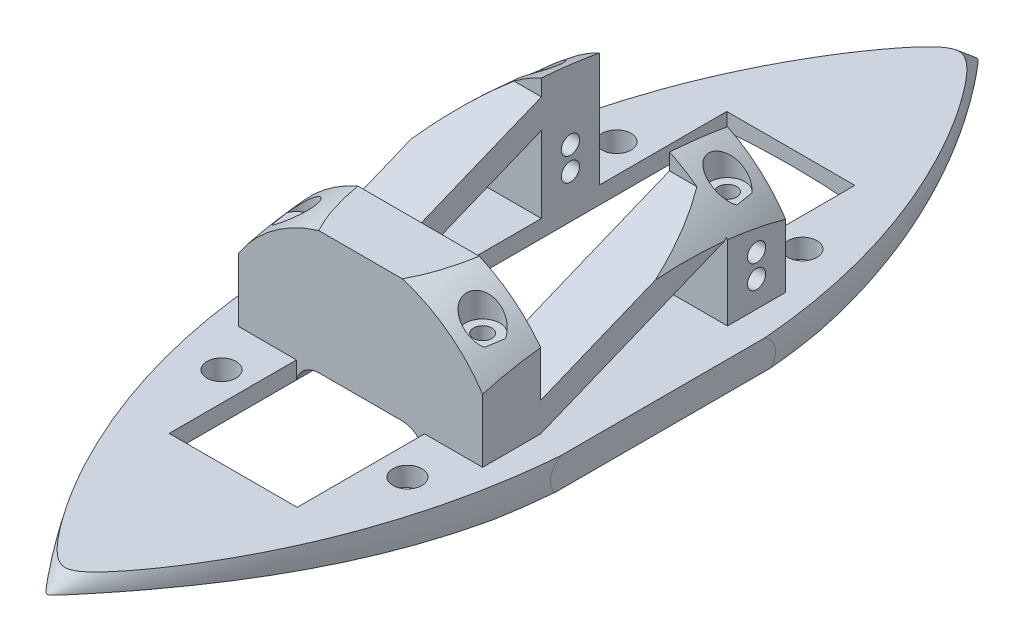
SolidWorks part; units mm, degrees
material "Custom Plastic"
ref_plane "Front Plane" through (0, 0, 0) normal (0, 0, 1) x (1, 0, 0)
ref_plane "Top Plane" through (0, 0, 0) normal (0, 1, 0) x (1, 0, 0)
ref_plane "Right Plane" through (0, 0, 0) normal (1, 0, 0) x (0, 0, -1)
sketch "Sketch2" plane through (0, 0, 0) normal (0, 0, 1) x (1, 0, 0)
  line L1 (-16.51, 1.5875) -> (16.51, 1.5875)
  line L2 (-16.51, 1.5875) -> (-16.51, -1.5875)
  line L3 (-16.51, -1.5875) -> (16.51, -1.5875)
  line L4 (16.51, 1.5875) -> (16.51, -1.5875)
  line L5 (-16.51, 1.5875) -> (16.51, -1.5875) construction
  line L6 (-16.51, -1.5875) -> (16.51, 1.5875) construction
  point P0 (0, 0)
  dimension "D1" = 3.175
  dimension "D2" = 33.02
extrude "Boss-Extrude1" add sketch "Sketch2" along normal blind 101.6
sketch "Sketch3" plane through (0, 0, 101.6) normal (0, 0, 1) x (1, 0, 0)
  line L0 (0, 0) -> (0, -78.359) construction
  circle A0 centre (0, -78.359) radius 78.359
  dimension "D1" = 78.359
extrude "Cut-Extrude1" cut sketch "Sketch3" against normal through all
sketch "Sketch5" plane through (0, 1.5875, 0) normal (0, 1, 0) x (1, 0, 0)
  line L0 (0, 0) -> (0, -34.925) construction
  line L1 (6.9977, -44.4246) -> (10.1727, -44.4246) construction
  line L2 (-6.9977, -25.4254) -> (6.9977, -25.4254) construction
  line L3 (-6.9977, -25.4254) -> (-6.9977, -44.4246) construction
  line L4 (-6.9977, -44.4246) -> (6.9977, -44.4246) construction
  line L5 (6.9977, -25.4254) -> (6.9977, -44.4246) construction
  line L6 (-6.9977, -25.4254) -> (6.9977, -44.4246) construction
  line L7 (-6.9977, -44.4246) -> (6.9977, -25.4254) construction
  line L8 (10.1727, -44.4246) -> (10.1727, -37.4142) construction
  line L9 (-13.3477, -40.5892) -> (-6.9977, -40.5892)
  line L10 (13.3477, -40.5892) -> (6.9977, -40.5892)
  line L11 (13.3477, -40.5892) -> (13.3477, -34.2392)
  line L12 (13.3477, -34.2392) -> (6.9977, -34.2392)
  line L13 (6.9977, -40.5892) -> (6.9977, -34.2392)
  line L14 (13.3477, -40.5892) -> (6.9977, -34.2392) construction
  line L15 (13.3477, -34.2392) -> (6.9977, -40.5892) construction
  line L16 (-6.9977, -40.5892) -> (-6.9977, -34.2392)
  line L17 (-13.3477, -40.5892) -> (-6.9977, -34.2392) construction
  line L18 (-13.3477, -34.2392) -> (-6.9977, -40.5892) construction
  line L19 (-13.3477, -34.2392) -> (-6.9977, -34.2392)
  line L20 (-13.3477, -40.5892) -> (-13.3477, -34.2392)
  line L21 (-10.1727, -44.4246) -> (-10.1727, -37.4142) construction
  line L22 (-6.9977, -44.4246) -> (-10.1727, -44.4246) construction
  line L23 (-16.51, -50.8) -> (16.51, -50.8) construction
  line L24 (-16.51, -101.6) -> (-16.51, 0) construction
  line L25 (16.51, -101.6) -> (16.51, 0) construction
  line L26 (-13.3477, -61.0108) -> (-6.9977, -61.0108)
  line L27 (-13.3477, -67.3608) -> (-6.9977, -61.0108) construction
  line L28 (-13.3477, -61.0108) -> (-6.9977, -67.3608) construction
  line L29 (-6.9977, -61.0108) -> (-6.9977, -67.3608)
  line L30 (-13.3477, -67.3608) -> (-6.9977, -67.3608)
  line L31 (-13.3477, -61.0108) -> (-13.3477, -67.3608)
  line L32 (13.3477, -67.3608) -> (6.9977, -61.0108) construction
  line L33 (13.3477, -61.0108) -> (6.9977, -67.3608) construction
  line L34 (6.9977, -61.0108) -> (6.9977, -67.3608)
  line L35 (13.3477, -67.3608) -> (6.9977, -67.3608)
  line L36 (13.3477, -61.0108) -> (13.3477, -67.3608)
  line L37 (13.3477, -61.0108) -> (6.9977, -61.0108)
  dimension "D1" = 13.9954
  dimension "D2" = 18.9992
  dimension "D3" = 34.925
  dimension "D4" = 3.175
  dimension "D5" = 7.0104
  dimension "D6" = 6.35
extrude "Boss-Extrude2" add sketch "Sketch5" along normal blind 15.24
sketch "Sketch6" plane through (13.3477, 0, 0) normal (1, 0, 0) x (0, 0, -1)
  line L0 (-61.0108, 1.5875) -> (-40.5892, 1.5875) construction
  line L1 (-40.5892, 1.5875) -> (-40.5892, 9.923) construction
  line L2 (-40.5892, 16.8275) -> (-40.5892, 1.5875) construction
  line L3 (-40.5892, 9.923) -> (-40.5892, 13.098) construction
  line L4 (-61.0108, 1.5875) -> (-61.0108, 4.7625) construction
  line L5 (-61.0108, 16.8275) -> (-61.0108, 1.5875) construction
  line L10 (-61.0108, 1.5875) -> (-61.0108, 4.7625)
  line L11 (-61.0108, 1.5875) -> (-40.5892, 9.923)
  line L12 (-61.0108, 4.7625) -> (-40.5892, 13.098)
  line L13 (-40.5892, 9.923) -> (-40.5892, 13.098)
  dimension "D1" = 8.3355
  dimension "D2" = 3.175
sketch "Sketch13" plane through (6.9977, 0, 0) normal (-1, 0, 0) x (0, 0, 1)
  line L0 (67.3608, 16.8275) -> (67.3608, 1.5875) construction
  line L9 (61.0108, 1.5875) -> (67.3608, 1.5875)
  line L10 (61.0108, 1.5875) -> (61.0108, 15.0495)
  line L11 (61.0108, 15.0495) -> (67.3608, 15.0495)
  line L12 (67.3608, 1.5875) -> (67.3608, 15.0495)
  dimension "D1" = 13.462
extrude "Boss-Extrude5" add sketch "Sketch13" along normal up to surface (13.9954 mm away) up to face at (-6.9977, 9.2075, 37.4142)
extrude "Boss-Extrude3" add sketch "Sketch6" against normal blind 6.35
sketch "Sketch4" plane through (0, 0, 0) normal (1, 0, 0) x (0, 0, -1)
  line L0 (0, 0) -> (-48.26, 0) construction
  line L1 (-48.26, 0) -> (-48.26, 16.51) construction
  line L2 (-48.26, 16.51) -> (-53.34, 16.51)
  line L3 (-50.8, 16.51) -> (-50.8, 0) construction
  line L4 (-48.26, 0) -> (-53.34, 0) construction
  line L5 (-101.6, 0) -> (-53.34, 0) construction
  line L6 (0, 0) -> (-101.6, 0) construction
  line L7 (0, 0) -> (0, -0.254) construction
  line L8 (0, -1.5875) -> (0, 1.5875) construction
  line L9 (0, -0.254) -> (-101.6, -0.254) construction
  line L10 (0, 0) -> (0, 25.4)
  line L11 (0, 25.4) -> (-101.6, 25.4)
  line L12 (-101.6, 25.4) -> (-101.6, 0)
  arc A0 (-48.26, 16.51) -> (0, 0) centre (-45.1787, -53.272) cw
  arc A1 (-53.34, 16.51) -> (-101.6, 0) centre (-56.4213, -53.272) ccw
  dimension "D3" = 69.85
  dimension "D5" = 0.254
  dimension "D1" = 48.26
  dimension "D2" = 16.51
  dimension "D4" = 2.54
  dimension "D6" = 101.6
  dimension "D7" = 25.4
mirror "Mirror4" about plane through (0, 0, 0) normal (1, 0, 0) of "Boss-Extrude3"
revolve "Cut-Revolve1" cut sketch "Sketch4" angle 100 about L9 other way angle 100
sketch "Sketch7" plane through (0, 1.5875, 0) normal (0, 1, 0) x (1, 0, 0)
  line L0 (0, 0) -> (0, -50.8) construction
  line L2 (-6.9977, -81.28) -> (6.9977, -81.28)
  line L3 (-6.9977, -81.28) -> (-6.9977, -20.32)
  line L4 (-6.9977, -20.32) -> (6.9977, -20.32)
  line L5 (6.9977, -81.28) -> (6.9977, -20.32)
  line L6 (-6.9977, -81.28) -> (6.9977, -20.32) construction
  line L7 (-6.9977, -20.32) -> (6.9977, -81.28) construction
  dimension "D1" = 50.8
  dimension "D2" = 13.9954
  dimension "D3" = 60.96
extrude "Cut-Extrude2" cut sketch "Sketch7" against normal up to next
sketch "Sketch8" plane through (13.3477, 0, 0) normal (1, 0, 0) x (0, 0, -1)
  line L0 (0, 0) -> (-34.2392, 0) construction
  line L1 (-37.4142, 0) -> (-37.4142, 6.985) construction
  line L2 (-34.2392, 0) -> (-40.5892, 0) construction
  line L3 (-40.5892, 0) -> (-40.5892, 1.5875) construction
  line L4 (-34.2392, 0) -> (-34.2392, 1.5875) construction
  line L5 (-34.2392, 8.5142) -> (-34.2392, 1.5875) construction
  line L6 (-37.4142, 0) -> (-37.4142, 4.445) construction
  line L7 (-40.5892, 9.7508) -> (-40.5892, 1.5875) construction
  circle A0 centre (-37.4142, 6.985) radius 1
  circle A1 centre (-37.4142, 4.445) radius 1
  dimension "D3" = 2
  dimension "D4" = 2
  dimension "D1" = 6.985
  dimension "D2" = 4.445
extrude "Cut-Extrude3" cut sketch "Sketch8" against normal up to surface (26.6954 mm away) and the other way through all up to face at (-13.3477, 5.5146, 38.208)
sketch "Sketch9" plane through (0, 1.5875, 0) normal (0, 1, 0) x (1, 0, 0)
  line L0 (-16.51, -50.8) -> (-10.16, -50.8) construction
  line L1 (-16.51, -61.9559) -> (-16.51, -39.6441) construction
  line L2 (-10.16, -50.8) -> (16.51, -50.8) construction
  line L3 (-10.16, -29.21) -> (-10.16, -72.39) construction
  line L5 (16.51, -61.9559) -> (16.51, -39.6441) construction
  line L6 (0, -20.32) -> (0, -81.28) construction
  line L7 (6.9977, -20.32) -> (-6.9977, -20.32) construction
  line L8 (-6.9977, -81.28) -> (6.9977, -81.28) construction
  line L9 (16.51, -50.8) -> (10.16, -50.8) construction
  line L10 (10.16, -29.21) -> (10.16, -72.39) construction
  circle A1 centre (-10.16, -72.39) radius 1.5875
  circle A2 centre (-10.16, -29.21) radius 1.5875
  circle A3 centre (10.16, -72.39) radius 1.5875
  circle A4 centre (10.16, -29.21) radius 1.5875
  dimension "D4" = 3.175
  dimension "D1" = 6.35
  dimension "D2" = 21.59
extrude "Cut-Extrude4" cut sketch "Sketch9" against normal up to next
sketch "Sketch11" plane through (0, 1.5875, 0) normal (0, 1, 0) x (1, 0, 0)
  line L0 (-6.9977, -37.4142) -> (-13.3477, -37.4142) construction
  line L1 (-6.9977, -40.5892) -> (-6.9977, -34.2392) construction
  line L2 (-13.3477, -34.2392) -> (-13.3477, -40.5892) construction
  line L3 (6.9977, -37.4142) -> (13.3477, -37.4142) construction
  line L4 (6.9977, -34.2392) -> (6.9977, -40.5892) construction
  line L5 (13.3477, -40.5892) -> (13.3477, -34.2392) construction
  line L6 (-16.51, -50.8) -> (16.51, -50.8) construction
  line L7 (-16.51, -61.9559) -> (-16.51, -39.6441) construction
  line L8 (16.51, -61.9559) -> (16.51, -39.6441) construction
  line L9 (-10.1727, -37.4142) -> (-10.1727, -50.8) construction
  line L10 (-10.1727, -50.8) -> (0, -50.8) construction
  circle A0 centre (-10.1727, -37.4142) radius 1.905
  circle A1 centre (10.1727, -37.4142) radius 1.905
  circle A2 centre (10.1727, -64.1858) radius 1.905
  circle A3 centre (-10.1727, -64.1858) radius 1.905
  dimension "D1" = 3.81
  dimension "D2" = 3.81
extrude "Cut-Extrude5" cut sketch "Sketch11" along normal up to next from offset 9.525
sketch "Sketch12" plane through (0, 11.1125, 0) normal (0, 1, 0) x (1, 0, 0)
  line L0 (16.51, -50.8) -> (-16.51, -50.8) construction
  line L1 (16.51, -61.9559) -> (16.51, -39.6441) construction
  line L4 (-16.51, -61.9559) -> (-16.51, -39.6441) construction
  line L5 (0, 0) -> (0, -101.5995) construction
  circle A0 centre (10.1727, -64.1858) radius 1
  circle A2 centre (-10.1727, -64.1858) radius 1
  circle A3 centre (-10.1727, -37.4142) radius 1
  circle A4 centre (10.1727, -37.4142) radius 1
  spline S0 degree 3 poles (15.693, -68.6707) (15.1546, -71.7346) (14.4205, -74.727) (12.5726, -80.5748) (11.4587, -83.4301) (9.4961, -87.6099) (8.7931, -88.9859) (7.2865, -91.7028) (6.4868, -93.0362) (4.7992, -95.6451) (3.9101, -96.923) (2.5111, -98.7907) (2.0341, -99.4057) (1.2991, -100.3125) (1.0513, -100.6127) (0.6686, -101.0534) (0.5398, -101.1996) (0.3341, -101.4064) (0.2638, -101.4746) (0.1436, -101.5577) (0.1002, -101.5823) (0.0055, -101.6049) (-0.0455, -101.5994) (-0.1361, -101.5635) (-0.1772, -101.5361) (-0.2543, -101.4772) (-0.2906, -101.4451) (-0.3965, -101.3462) (-0.4634, -101.2762) (-0.6612, -101.0631) (-0.7881, -100.917) (-1.1654, -100.4755) (-1.4109, -100.1761) (-2.1394, -99.2713) (-2.6121, -98.6587) (-3.998, -96.7989) (-4.8783, -95.5283) (-6.5536, -92.9271) (-7.3444, -91.6026) (-8.8284, -88.9177) (-9.5227, -87.5556) (-11.4654, -83.4108) (-12.5741, -80.57) (-13.9581, -76.1903) (-14.3727, -74.7106) (-15.1069, -71.7107) (-15.4252, -70.1948) (-15.693, -68.6707) knots 0 0 0 0 0.125 0.125 0.25 0.25 0.3125 0.3125 0.375 0.375 0.4375 0.4375 0.46875 0.46875 0.484375 0.484375 0.492188 0.492188 0.496094 0.496094 0.498047 0.498047 0.5 0.5 0.501953 0.501953 0.503906 0.503906 0.507813 0.507813 0.515625 0.515625 0.53125 0.53125 0.5625 0.5625 0.625 0.625 0.6875 0.6875 0.75 0.75 0.875 0.875 0.9375 0.9375 1 1 1 1 construction
  dimension "D1" = 2
extrude "Cut-Extrude6" cut sketch "Sketch12" against normal blind 4.445
fillet "Fillet1" radius 2.54 2 edges at (-6.9977, 1.5875, 64.1858) (6.9977, 1.5875, 64.1858)
